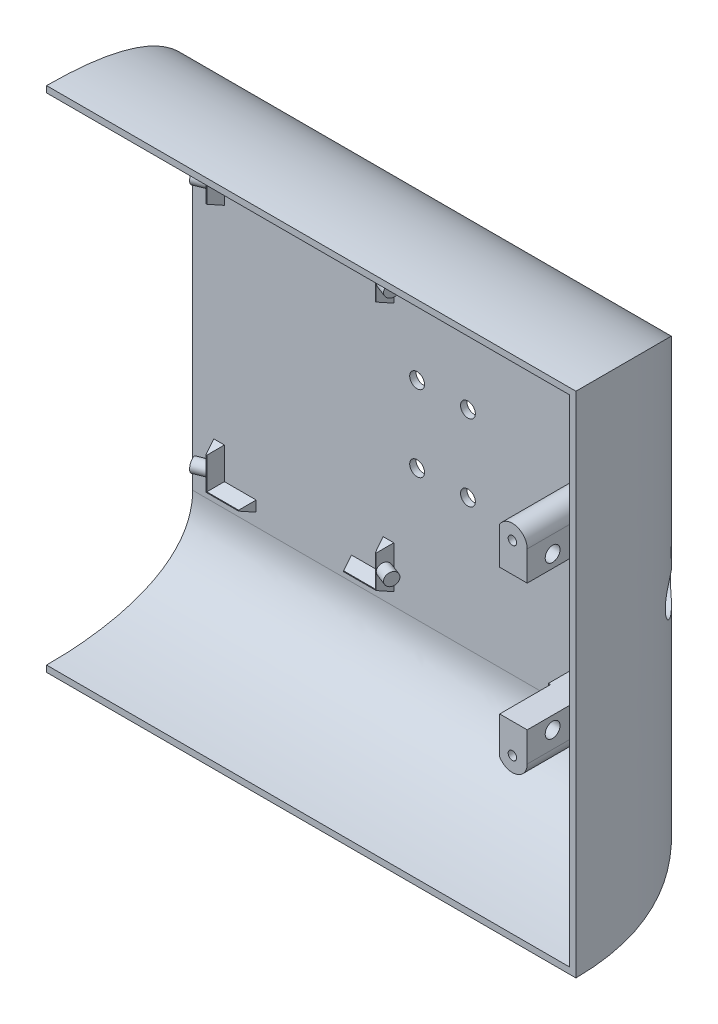
SolidWorks part; units mm, degrees
ref_plane "Plan de face" through (0, 0, 0) normal (0, 0, 1) x (1, 0, 0)
ref_plane "Plan de dessus" through (0, 0, 0) normal (0, 1, 0) x (1, 0, 0)
ref_plane "Plan de droite" through (0, 0, 0) normal (1, 0, 0) x (0, 0, -1)
sketch "Esquisse1" plane through (0, 0, 0) normal (0, 0, 1) x (1, 0, 0)
  line L1 (100.6491, 73.8649) -> (-4.3509, 73.8649)
  line L2 (100.6491, 73.8649) -> (100.6491, -6.1351)
  line L3 (100.6491, -6.1351) -> (-4.3509, -6.1351)
  line L4 (-4.3509, 73.8649) -> (-4.3509, 33.8649)
  line L7 (-4.3509, 33.8649) -> (-4.3509, -6.1351)
  dimension "D1" = 105
  dimension "D2" = 80
extrude "Boss.-Extru.1" add sketch "Esquisse1" along normal blind 1.5
sketch "Esquisse3" plane through (0, 0, 1.5) normal (0, 0, 1) x (1, 0, 0)
  line L0 (100.6491, 33.8649) -> (-4.3509, 33.8649) construction
  line L1 (100.6491, -6.1351) -> (100.6491, 73.8649) construction
  line L2 (60.6491, 66.3622) -> (60.6491, 22.1054) construction
  line L3 (48.6491, 66.3622) -> (48.6491, 22.1054) construction
  line L4 (-4.3509, 73.8649) -> (-4.3509, -6.1351) construction
  circle A1 centre (48.6491, 42.8649) radius 1.75
  circle A2 centre (48.6491, 24.8649) radius 1.75
  circle A3 centre (60.6491, 24.8649) radius 1.75
  circle A4 centre (60.6491, 42.8649) radius 1.75
  dimension "D1" = 3.5
  dimension "D2" = 3.5
  dimension "D3" = 3.5
  dimension "D4" = 3.5
  dimension "D7" = 9
  dimension "D8" = 9
  dimension "D9" = 9
  dimension "D5" = 12
  dimension "D6" = 9
  dimension "D10" = 40
extrude "Enlèv. mat.-Extru.1" cut sketch "Esquisse3" against normal up to next
sketch "Esquisse19" plane through (0, 0, 0) normal (0, 0, -1) x (-1, 0, 0)
  line L0 (4.3509, -6.1351) -> (-100.6491, -6.1351)
  line L1 (-100.6491, -6.1351) -> (-100.6491, 73.8649)
  line L2 (-100.6491, 73.8649) -> (4.3509, 73.8649)
sketch "Esquisse4" plane through (0, 0, 1.5) normal (0, 0, -1) x (-1, 0, 0)
  line L0 (-100.6491, 33.8649) -> (-3.0389, 33.8649) construction
  line L1 (-3.1491, -0.6351) -> (-40.6491, -0.6351) construction
  line L2 (-3.1491, -0.6351) -> (-3.1491, 65.8649) construction
  line L3 (-5.6491, 68.3649) -> (-38.1491, 68.3649) construction
  line L4 (-3.1491, 65.8649) -> (-3.1491, 55.8649)
  line L5 (-100.6491, -6.1351) -> (-100.6491, 73.8649) construction
  line L6 (-3.1491, 55.8649) -> (-0.6491, 55.8649)
  line L7 (-0.6491, -3.1351) -> (-43.1491, -3.1351) construction
  line L8 (-0.6491, -3.1351) -> (-0.6491, 65.8649) construction
  line L9 (-5.6491, 70.8649) -> (-38.1491, 70.8649) construction
  line L10 (-43.1491, -3.1351) -> (-43.1491, 65.8649) construction
  line L11 (-40.6491, -0.6351) -> (-40.6491, 65.8649) construction
  line L12 (-0.6491, 55.8649) -> (-0.6491, 65.8649)
  line L13 (-0.6491, 65.8649) -> (-3.1491, 65.8649)
  line L14 (-5.6491, 70.8649) -> (-5.6491, 68.3649)
  line L15 (-40.6491, 65.8649) -> (-40.6491, 55.8649)
  line L16 (-40.6491, 55.8649) -> (-43.1491, 55.8649)
  line L17 (-43.1491, 65.8649) -> (-40.6491, 65.8649)
  line L18 (-38.1491, 70.8649) -> (-38.1491, 68.3649)
  line L19 (-43.1491, 55.8649) -> (-43.1491, 65.8649)
  line L20 (-40.6491, 6.8649) -> (-43.1491, 6.8649)
  line L21 (-43.1491, 6.8649) -> (-43.1491, -3.1351)
  line L22 (-43.1491, -3.1351) -> (-33.1491, -3.1351)
  line L23 (-33.1491, -3.1351) -> (-33.1491, -0.6351)
  line L24 (-33.1491, -0.6351) -> (-40.6491, -0.6351)
  line L25 (-10.6491, -0.6351) -> (-10.6491, -3.1351)
  line L26 (-10.6491, -3.1351) -> (-0.6491, -3.1351)
  line L27 (-0.6491, -3.1351) -> (-0.6491, 6.8649)
  line L28 (-0.6491, 6.8649) -> (-3.1491, 6.8649)
  line L29 (-3.1491, 6.8649) -> (-3.1491, -0.6351)
  line L30 (-3.1491, -0.6351) -> (-10.6491, -0.6351)
  line L31 (-5.6491, 70.8649) -> (-15.6491, 70.8649)
  line L32 (-15.6491, 70.8649) -> (-15.6491, 68.3649)
  line L33 (-15.6491, 68.3649) -> (-5.6491, 68.3649)
  line L34 (-38.1491, 70.8649) -> (-28.1491, 70.8649)
  line L35 (-28.1491, 70.8649) -> (-28.1491, 68.3649)
  line L36 (-28.1491, 68.3649) -> (-38.1491, 68.3649)
  line L37 (-40.6491, 6.8649) -> (-40.6491, -0.6351)
  circle A0 centre (-48.6491, 24.8649) radius 1.75 construction
  point P3 (-70.3996, 0.9688)
  point P4 (-51.6001, 33.8649)
  point P14 (-70.3501, 69.9688)
  dimension "D2" = 2.5
  dimension "D3" = 2.5
  dimension "D4" = 2.5
  dimension "D5" = 34.5
  dimension "D6" = 5.5
  dimension "D7" = 2.5
  dimension "D8" = 32.5
  dimension "D9" = 2.5
  dimension "D10" = 2.5
  dimension "D11" = 34.5
  dimension "D12" = 2.5
  dimension "D13" = 2.5
  dimension "D14" = 10
  dimension "D15" = 10
  dimension "D16" = 10
  dimension "D17" = 10
  dimension "D18" = 10
  dimension "D19" = 10
  dimension "D20" = 10
  dimension "D21" = 10
extrude "Boss.-Extru.2" add sketch "Esquisse4" against normal blind 3 draft 21
sketch "Esquisse7" plane through (-4.3509, 0, 0) normal (1, 0, 0) x (0, 0, -1)
  line L0 (0, -6.1351) -> (0, 73.8649) construction
  line L1 (-1.5, -6.1351) -> (-1.5, 73.8649) construction
  line L4 (-1.5, 73.8649) -> (0, 73.8649) construction
  line L6 (-1.5, 73.8649) -> (0, 73.8649)
  line L7 (-36, 93.8649) -> (-36, 92.3649)
  spline S0 degree 3 poles (0, 73.8649) (0, 81.3378) (-5.0996, 93.8032) (-36, 93.8649) knots 0 0 0 0 1 1 1 1
  spline S1 degree 3 poles (-36, 92.3649) (-32.8249, 92.3649) (-1.5, 92.9097) (-1.5, 73.8649) knots 0 0 0 0 1 1 1 1
  dimension "D2" = 20
  dimension "D1" = 36
sweep "Balayage1" add profiles "Esquisse7" path "Esquisse19"
sketch "Esquisse8" plane through (0, 0, 0) normal (0, 0, -1) x (-1, 0, 0)
  line L0 (-100.6491, 33.8649) -> (-183.7283, 33.8649) construction
  line L1 (-100.6491, -6.1351) -> (-100.6491, 73.8649) construction
  line L2 (-105.6491, 64.6793) -> (-105.6491, 3.4231) construction
  line L3 (-100.6491, 73.8649) -> (-100.6491, -6.1351) construction
  circle A0 centre (-105.6491, 55.8649) radius 1
  circle A1 centre (-105.6491, 11.8649) radius 1
  point P2 (-100.6491, 33.8649)
  dimension "D3" = 2
  dimension "D4" = 2
  dimension "D1" = 22
  dimension "D2" = 22
  dimension "D5" = 5
extrude "Enlèv. mat.-Extru.2" cut sketch "Esquisse8" against normal up to next
sketch "Esquisse9" plane through (0, 0, 36) normal (0, 0, 1) x (1, 0, 0)
  line L2 (102.1491, 55.8649) -> (102.1491, 48.8649)
  line L3 (102.1491, 48.8649) -> (109.1491, 48.8649)
  line L4 (109.1491, 55.8649) -> (109.1491, 48.8649)
  line L6 (109.1491, 11.8649) -> (109.1491, 18.8649)
  line L7 (109.1491, 18.8649) -> (102.1491, 18.8649)
  line L8 (102.1491, 11.8649) -> (102.1491, 18.8649)
  circle A0 centre (105.6491, 55.8649) radius 1
  circle A1 centre (105.6491, 11.8649) radius 1
  arc A2 (102.1491, 11.8649) -> (109.1491, 11.8649) centre (105.6491, 11.8649) ccw
  arc A3 (109.1491, 55.8649) -> (102.1491, 55.8649) centre (105.6491, 55.8649) ccw
  dimension "D1" = 2.5
  dimension "D2" = 2.5
  dimension "D3" = 2
  dimension "D4" = 2
  dimension "D5" = 30
extrude "Boss.-Extru.3" add sketch "Esquisse9" against normal up to next
sketch "Esquisse10" plane through (0, 0, 36) normal (0, 0, 1) x (1, 0, 0)
  line L0 (102.6491, 10.0621) -> (102.6491, 18.8649)
  line L2 (102.6491, 48.8649) -> (102.6491, 57.6676)
  line L3 (102.1491, 48.8649) -> (109.1491, 48.8649) construction
  line L4 (102.1491, 55.8649) -> (102.1491, 48.8649) construction
  line L5 (102.1491, 55.8649) -> (102.1491, 48.8649)
  line L6 (102.6491, 48.8649) -> (102.1491, 48.8649)
  line L7 (109.1491, 18.8649) -> (102.1491, 18.8649) construction
  line L8 (102.1491, 18.8649) -> (102.1491, 11.8649) construction
  line L9 (102.6491, 18.8649) -> (102.1491, 18.8649)
  line L10 (102.1491, 18.8649) -> (102.1491, 11.8649)
  line L11 (100.6491, 73.8649) -> (100.6491, -6.1351) construction
  circle A0 centre (105.6491, 55.8649) radius 3.5 construction
  circle A1 centre (105.6491, 11.8649) radius 3.5 construction
  arc A2 (109.1491, 55.8649) -> (102.1491, 55.8649) centre (105.6491, 55.8649) ccw construction
  arc A3 (102.1491, 11.8649) -> (109.1491, 11.8649) centre (105.6491, 11.8649) ccw construction
  arc A4 (102.6491, 57.6676) -> (102.1491, 55.8649) centre (105.6491, 55.8649) ccw
  arc A5 (102.1491, 11.8649) -> (102.6491, 10.0621) centre (105.6491, 11.8649) ccw
  dimension "D1" = 2
extrude "Enlèv. mat.-Extru.3" cut sketch "Esquisse10" against normal blind 12
sketch "Esquisse11" plane through (102.6491, 0, 0) normal (-1, 0, 0) x (0, 0, 1)
  line L0 (30, 48.8649) -> (30, 18.8649) construction
  line L4 (24, 48.8649) -> (36, 48.8649) construction
  line L5 (24, 18.8649) -> (36, 18.8649) construction
  line L6 (30, 48.8649) -> (30, 51.8649) construction
  line L7 (30, 15.8649) -> (30, 18.8649) construction
  circle A0 centre (30, 51.8649) radius 1.75
  circle A1 centre (30, 15.8649) radius 1.75
  point P6 (30, 48.8649)
  point P7 (30, 18.8649)
  dimension "D1" = 3.5
  dimension "D2" = 3.5
  dimension "D3" = 36
extrude "Enlèv. mat.-Extru.4" cut sketch "Esquisse11" against normal up to next
sketch "Esquisse16" plane through (102.1491, 0, 0) normal (-1, 0, 0) x (0, 0, 1)
  line L1 (1.5673, 39.8649) -> (16.5673, 39.8649)
  line L2 (1.5673, 39.8649) -> (1.5673, 27.8649)
  line L3 (1.5673, 27.8649) -> (16.5673, 27.8649)
  line L4 (16.5673, 39.8649) -> (16.5673, 27.8649)
  line L5 (1.5673, 48.8649) -> (1.5673, 55.8649) construction
  line L6 (1.5673, 48.8649) -> (24, 48.8649) construction
  line L7 (1.5673, 18.8649) -> (24, 18.8649) construction
  line L8 (16.5673, 39.8649) -> (16.5673, 48.8649) construction
  line L9 (16.5673, 27.8649) -> (16.5673, 18.8649) construction
  dimension "D1" = 15
  dimension "D2" = 12
extrude "Boss.-Extru.4" add sketch "Esquisse16" against normal up to next
sketch "Esquisse12" plane through (157.424, 0, -57.2977) normal (0.9397, 0, -0.342) x (-0.342, 0, -0.9397)
  circle A0 centre (-44.7183, 33.8649) radius 4.25
  dimension "D1" = 8.5
extrude "Enlèv. mat.-Extru.5" cut sketch "Esquisse12" against normal up to surface (73.5516 mm away) up to face at (102.1491, 33.8649, 9.0673)
sketch "Esquisse17" plane through (0, 0, 16.5673) normal (0, 0, 1) x (1, 0, 0)
  line L0 (116.7579, 39.8649) -> (102.1491, 39.8649) construction
  line L1 (107.1491, 39.8649) -> (111.1491, 39.8649)
  line L2 (107.1491, 39.8649) -> (107.1491, 27.8649)
  line L3 (107.1491, 27.8649) -> (111.1491, 27.8649)
  line L4 (111.1491, 39.8649) -> (111.1491, 27.8649)
  line L5 (116.7579, 27.8649) -> (102.1491, 27.8649) construction
  line L6 (102.1491, 27.8649) -> (102.1491, 39.8649) construction
  point P8 (102.1491, 33.8649)
  dimension "D1" = 4
  dimension "D2" = 5
extrude "Enlèv. mat.-Extru.6" cut sketch "Esquisse17" against normal blind 8
sketch "Esquisse20" plane through (0.0639, 0, -0.0245) normal (-0.9336, 0, 0.3584) x (0.3584, 0, 0.9336)
  line L0 (4.8464, 57.0165) -> (4.8464, 64.7133) construction
  line L1 (4.8464, 60.8649) -> (2.5987, 60.8649) construction
  line L2 (4.8464, -1.9835) -> (4.8464, 5.7133) construction
  line L3 (4.8464, 1.8649) -> (4.8918, 1.8649) construction
  circle A0 centre (3.3464, 60.8649) radius 1.5
  circle A1 centre (3.3464, 1.8649) radius 1.5
  point P4 (4.8464, 60.8649)
  point P9 (4.8464, 1.8649)
  dimension "D1" = 3
  dimension "D2" = 3
extrude "Boss.-Extru.5" add sketch "Esquisse20" along normal blind 3
sketch "Esquisse21" plane through (38.1094, 0, 14.6288) normal (0.9336, 0, 0.3584) x (0.3584, 0, -0.9336)
  line L0 (10.8494, 64.7133) -> (10.8494, 57.0165) construction
  line L1 (10.8494, 5.7133) -> (10.8494, -1.9835) construction
  line L2 (10.8494, 1.8649) -> (-0.6031, 1.8649) construction
  line L3 (10.8494, 60.8649) -> (-0.9717, 60.8649) construction
  circle A0 centre (12.3494, 60.8649) radius 1.5
  circle A1 centre (12.3494, 1.8649) radius 1.5
  point P4 (10.8494, 60.8649)
  point P5 (10.8494, 1.8649)
  dimension "D1" = 3
  dimension "D2" = 3
extrude "Boss.-Extru.6" add sketch "Esquisse21" along normal blind 3
